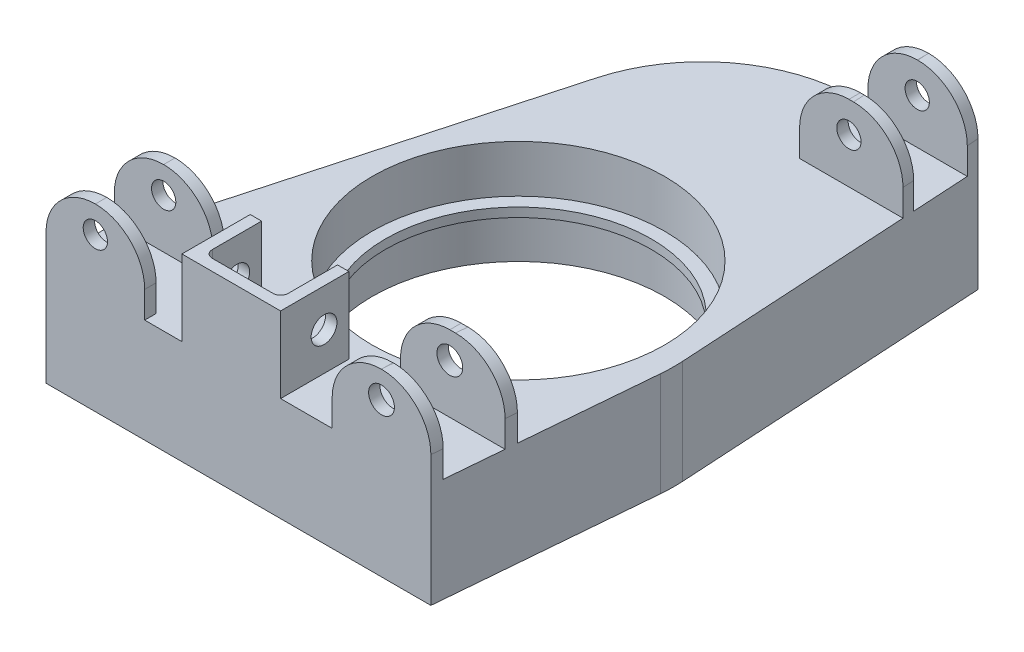
SolidWorks part; units mm, degrees
ref_plane "Front Plane" through (0, 0, 0) normal (0, 0, 1) x (1, 0, 0)
ref_plane "Top Plane" through (0, 0, 0) normal (0, 1, 0) x (1, 0, 0)
ref_plane "Right Plane" through (0, 0, 0) normal (1, 0, 0) x (0, 0, -1)
sketch "Sketch1" plane through (0, 0, 0) normal (0, 1, 0) x (1, 0, 0)
  line L0 (-78.3166, -79.7284) -> (50.4493, -79.7284)
  line L1 (56.8393, -5.2886) -> (50.4493, 103.3395)
  line L2 (50.4493, 103.3395) -> (9.0638, 103.3395)
  line L3 (-39.909, 66.0414) -> (-72.7449, -53.0584)
  line L4 (50.4493, 103.3395) -> (50.4493, -79.7284) construction
  line L5 (50.4493, -79.7284) -> (56.8393, -5.2886)
  line L6 (-78.3166, -79.7284) -> (-78.3166, -53.0584)
  line L7 (-78.3166, -53.0584) -> (-72.7449, -53.0584)
  circle A0 centre (0, 0) radius 48.895
  circle A2 centre (0, 0) radius 120.65
  arc A3 (9.0638, 103.3395) -> (-39.909, 66.0414) centre (9.0638, 52.5395) ccw
  point P10 (0, -48.895)
  point P11 (48.895, 0)
  point P16 (-48.895, 0)
  dimension "D2" = 97.79
  dimension "D3" = 7.62
  dimension "D4" = 8.89
  dimension "D5" = 26.67
  dimension "D1" = 241.3
  dimension "D6" = 50.8
extrude "Base" add sketch "Sketch1" along normal blind 34.798 contours L2 L3 L0 L1 A0 | L1 L4 A0 L5 region at (-76.0411, 0, 66.3934)
sketch "Sketch2" plane through (0, 34.798, 0) normal (0, 1, 0) x (1, 0, 0)
  line L0 (50.4493, 103.3395) -> (50.6734, 99.5295)
  line L1 (56.8393, -5.2886) -> (50.4493, 103.3395) construction
  line L2 (50.6734, 99.5295) -> (17.4293, 99.5295)
  line L3 (17.4293, 99.5295) -> (17.4293, 103.3395)
  line L4 (50.4493, 103.3395) -> (9.0638, 103.3395) construction
  line L5 (17.4293, 103.3395) -> (50.4493, 103.3395)
  line L6 (17.4293, -75.9184) -> (50.7764, -75.9184)
  line L7 (50.7764, -75.9184) -> (50.4493, -79.7284)
  line L8 (-78.3166, -79.7284) -> (50.4493, -79.7284) construction
  line L9 (50.4493, -79.7284) -> (17.4293, -79.7284)
  line L10 (17.4293, -79.7284) -> (17.4293, -75.9184)
  line L11 (17.4293, 103.3395) -> (17.4293, -79.7284) construction
  line L12 (50.4493, -79.7284) -> (56.8393, -5.2886) construction
  line L13 (17.4293, 80.4795) -> (17.4293, 76.6695)
  line L14 (17.4293, 76.6695) -> (52.0182, 76.6695)
  line L15 (52.0182, 76.6695) -> (51.794, 80.4795)
  line L16 (51.794, 80.4795) -> (17.4293, 80.4795)
  line L17 (-78.3166, -79.7284) -> (-78.3166, -53.0584) construction
  line L18 (17.4293, -53.0584) -> (52.7387, -53.0584)
  line L19 (17.4293, -53.0584) -> (17.4293, -56.8684)
  line L20 (17.4293, -56.8684) -> (52.4116, -56.8684)
  line L21 (52.7387, -53.0584) -> (52.4116, -56.8684)
  line L22 (-45.2966, -53.0584) -> (-78.3166, -53.0584)
  line L23 (-45.2966, -53.0584) -> (-45.2966, -56.8684)
  line L24 (-45.2966, -56.8684) -> (-78.3166, -56.8684)
  line L25 (-78.3166, -53.0584) -> (-78.3166, -56.8684)
  line L26 (-45.2966, -79.7284) -> (-45.2966, -60.0458) construction
  line L27 (-78.3166, -75.9184) -> (-45.2966, -75.9184)
  line L28 (-78.3166, -75.9184) -> (-78.3166, -79.7284)
  line L29 (-78.3166, -79.7284) -> (-45.2966, -79.7284)
  line L30 (-45.2966, -75.9184) -> (-45.2966, -79.7284)
  line L31 (-78.3166, -79.7284) -> (50.4493, -79.7284) construction
  dimension "D1" = 33.02
  dimension "D2" = 3.81
  dimension "D3" = 3.81
  dimension "D4" = 19.05
  dimension "D5" = 3.81
  dimension "D6" = 3.81
  dimension "D7" = 19.05
  dimension "D8" = 33.02
  dimension "D9" = 3.81
  dimension "D10" = 3.81
extrude "A-Arms" add sketch "Sketch2" along normal blind 25.4
fillet "Fillet a-arm tab f" radius 16.51 12 edges at (50.6128, 60.198, 77.8234) (52.5752, 60.198, 54.9634) (17.4293, 60.198, 77.8234) (17.4293, 60.198, 54.9634) (51.9061, 60.198, -78.5745) (50.5614, 60.198, -101.4345) (17.4293, 60.198, -78.5745) (17.4293, 60.198, -101.4345) (-78.3166, 60.198, 77.8234) (-45.2966, 60.198, 77.8234) (-45.2966, 60.198, 54.9634) (-78.3166, 60.198, 54.9634)
fillet "Fillet2" radius 50.8 1 edges at (56.8393, 17.399, 5.2886)
ref_plane "Plane1" through (0, 1, 0) normal (0, -1, 0) x (-1, 0, 0)
sketch "Sketch3" plane through (0, 1, 0) normal (0, -1, 0) x (-1, 0, 0)
  line L0 (43.8545, 51.7309) -> (51.7371, 53.9041)
  line L1 (39.909, 66.0414) -> (72.7449, -53.0584) construction
  line L2 (63.9719, -21.2377) -> (72.1885, -18.9724)
  line L3 (54.0145, 33.5988) -> (63.3923, -0.4157)
  line L4 (43.8545, 51.7309) -> (63.9719, -21.2377)
  circle A0 centre (0, 0) radius 71.12
  circle A1 centre (53.7624, 46.5582) radius 4.191
  circle A2 centre (70.1632, -11.6265) radius 4.191
  arc A3 (56.852, 39.5926) -> (51.7371, 53.9041) centre (53.7624, 46.5582) ccw
  arc A4 (72.1885, -18.9724) -> (69.039, -4.0899) centre (70.1632, -11.6265) ccw
  arc A5 (63.3923, -0.4157) -> (69.039, -4.0899) centre (68.2896, 0.9345) ccw
  arc A6 (54.0145, 33.5988) -> (56.852, 39.5926) centre (58.9118, 34.949) cw
  dimension "D1" = 60.452
  dimension "D2" = 142.24
  dimension "D3" = 8.382
  dimension "D4" = 8.382
  dimension "D5" = 15.24
  dimension "D6" = 15.24
  dimension "D7" = 5.08
extrude "Boss-Extrude3" add sketch "Sketch3" against normal blind 10 contours L3 A6 A3 A0 A1 L0 L4 L2 A2 A4 A5 | A0 A3 L0 A1 | L2 A4 A0 A2 region at (-57.0001, 1, -15.6865) region at (-49.7533, 1, -53.1565) region at (-69.0083, 1, 17.9571)
fillet "Fillet3" radius 12.7 2 edges at (-43.8545, 6, -51.7309) (-63.9719, 6, 21.2377)
sketch "Sketch6" plane through (0, 0, -103.3395) normal (0, 0, -1) x (-1, 0, 0)
  line L0 (-33.9251, 60.198) -> (-33.9251, 40.2979) construction
  circle A1 centre (-33.9251, 49.911) radius 4.064
  dimension "D1" = 15.113
  dimension "D2" = 8.128
extrude "Tab Holes 1" cut sketch "Sketch6" against normal blind 38.1
sketch "Sketch7" plane through (0, 0, 53.0584) normal (0, 0, -1) x (-1, 0, 0)
  line L0 (61.8066, 60.198) -> (61.8066, 34.798) construction
  line L4 (45.2966, 34.798) -> (72.7449, 34.798) construction
  circle A0 centre (61.8066, 51.308) radius 4.064
  point P2 (61.8066, 29.6031)
  point P5 (0, 0)
  point P6 (0, 0)
  point P9 (0, 0)
  dimension "D1" = 16.51
  dimension "D2" = 8.128
extrude "Tab Holes 2" cut sketch "Sketch7" against normal through all
ref_plane "midplane" through (0, 17.399, 0) normal (0, 1, 0) x (1, 0, 0)
sketch "Sketch8" plane through (0, 17.399, 0) normal (0, 1, 0) x (1, 0, 0)
  circle A0 centre (0, 0) radius 48.895
  circle A1 centre (0, 0) radius 44.45
extrude "mid-feature bearing" add sketch "Sketch8" along normal blind 1.524 and the other way blind 1.524
sketch "Sketch9" plane through (0, 34.798, 0) normal (0, 1, 0) x (1, 0, 0)
  line L0 (-45.2966, -79.7284) -> (17.4293, -79.7284) construction
  line L1 (-32.844, -79.7284) -> (0.176, -79.7284)
  line L2 (-32.844, -79.7284) -> (-32.844, -75.9184)
  line L3 (-32.844, -75.9184) -> (0.176, -75.9184)
  line L4 (0.176, -79.7284) -> (0.176, -75.9184)
  line L5 (-45.2966, -56.8684) -> (17.4293, -56.8684) construction
  line L6 (0.176, -75.9184) -> (-3.634, -75.9184)
  line L7 (0.176, -75.9184) -> (0.176, -56.8684)
  line L8 (0.176, -56.8684) -> (-3.634, -56.8684)
  line L9 (-3.634, -75.9184) -> (-3.634, -56.8684)
  line L10 (-32.844, -75.9184) -> (-29.034, -75.9184)
  line L11 (-32.844, -75.9184) -> (-32.844, -56.8684)
  line L12 (-32.844, -56.8684) -> (-29.034, -56.8684)
  line L13 (-29.034, -75.9184) -> (-29.034, -56.8684)
  line L14 (17.4293, -53.0584) -> (17.4293, -56.8684) construction
  point P15 (0, 0)
  point P16 (17.4293, -56.8684)
  line M30 (-45.2966, -79.7284) -> (17.4293, -79.7284)
  dimension "D1" = 3.81
  dimension "D2" = 3.81
  dimension "D3" = 3.81
  dimension "D4" = 25.4
extrude "Boss-Extrude5" add sketch "Sketch9" along normal blind 25.4 contours L3 L13 L12 L11 | L4 L3 L2 M30 | L9 L3 L7 L8 region at (-16.334, 34.798, 77.8234) region at (-30.939, 34.798, 66.3934) region at (-1.729, 34.798, 66.3934)
fillet "Pushrod Str" radius 2.54 2 edges at (-3.634, 47.498, 75.9184) (-29.034, 47.498, 75.9184)
sketch "Sketch10" plane through (-32.844, 0, 0) normal (-1, 0, 0) x (0, 0, 1)
  line L0 (56.8684, 47.498) -> (80.5175, 47.498) construction
  line L1 (56.8684, 60.198) -> (56.8684, 34.798) construction
  circle A0 centre (65.1913, 47.498) radius 4.318
  point P2 (69.1218, 45.72)
  point P3 (65.1913, 47.498)
  dimension "D1" = 8.3229
extrude "Pushrod Holes" cut sketch "Sketch10" against normal through all
mirror "Mirror2" [suppressed] of bodies 108
delete or keep bodies "Body-Delete/Keep 1" [suppressed] type delete bodies bodies 108
sketch "Sketch11" plane through (0, 0, 79.7284) normal (0, 0, -1) x (-1, 0, 0)
  line L0 (-33.9393, 60.198) -> (-33.9393, 34.798) construction
  line L2 (-17.4293, 34.798) -> (-50.4493, 34.798) construction
  line L3 (-50.4493, 43.688) -> (-50.4493, 0) construction
  circle A0 centre (-33.9393, 51.308) radius 4.318
  arc A1 (-17.4293, 43.688) -> (-33.909, 60.198) centre (-33.9393, 43.688) ccw construction
  dimension "D1" = 16.51
extrude "Tab Holes 3" cut sketch "Sketch11" along normal blind 50.8
ref_plane "Plane2" through (0, 0, -90.0045) normal (0, 0, -1) x (-1, 0, 0)
ref_axis "Axis1" through (33.9251, 49.911, -76.6695) along (0, 0, -1)
ref_point "top wishbont att pt"
ref_plane "Plane3" through (0, 0, 66.3934) normal (0, 0, -1) x (-1, 0, 0)
ref_axis "Axis2" through (33.9393, 51.308, 53.0584) along (0, 0, 1)
ref_point "Bottom Wish"
ref_axis "Axis3" through (-61.8066, 51.308, 56.8684) along (0, 0, -1)
ref_point "Anchor tierod"
